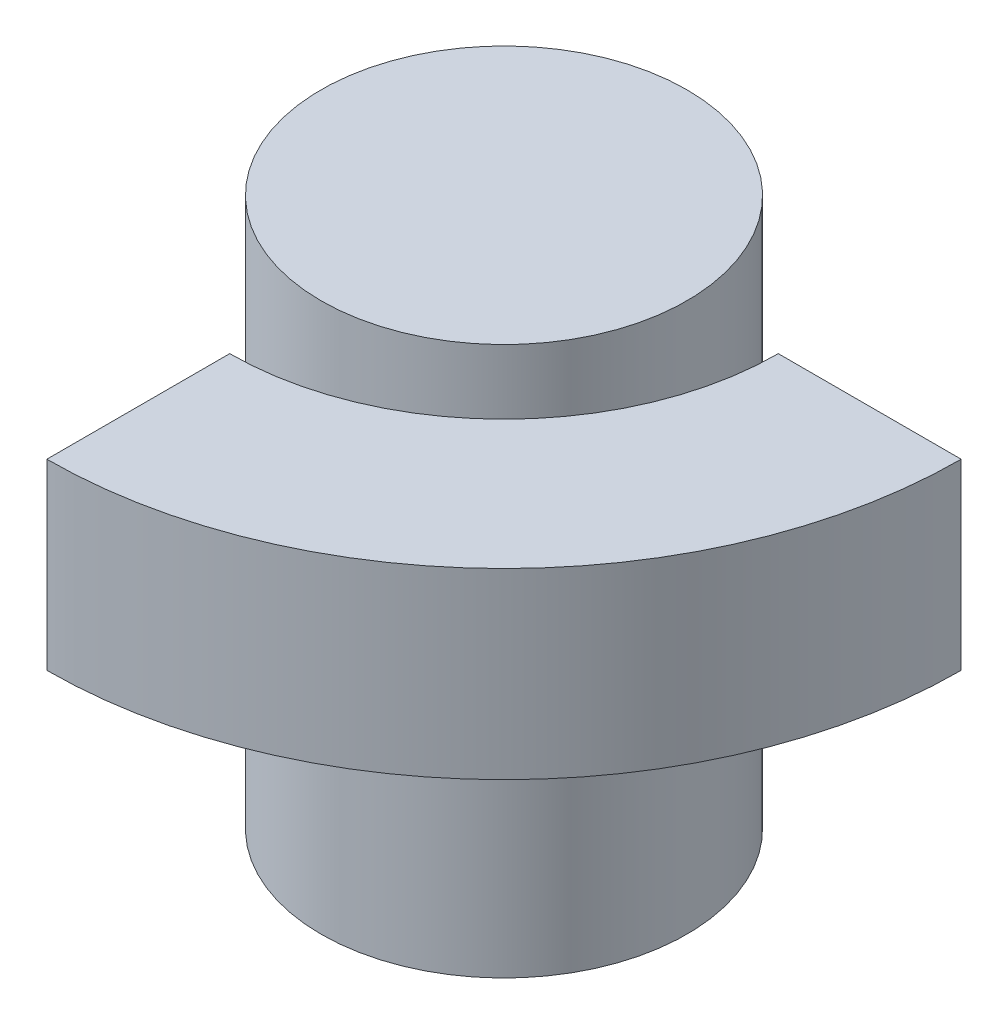
SolidWorks part; units mm, degrees
ref_plane "Front Plane" through (0, 0, 0) normal (0, 0, 1) x (1, 0, 0)
ref_plane "Top Plane" through (0, 0, 0) normal (0, 1, 0) x (1, 0, 0)
ref_plane "Right Plane" through (0, 0, 0) normal (1, 0, 0) x (0, 0, -1)
sketch "Sketch1" plane through (0, 0, 0) normal (0, 1, 0) x (1, 0, 0)
  circle A0 centre (20, 0) radius 10
extrude "Boss-Extrude1" add sketch "Sketch1" along normal blind 15 and the other way blind 15
sketch "Sketch2" plane through (0, 0, 0) normal (0, 0, 1) x (1, 0, 0)
  line L1 (35, 5) -> (45, 5)
  line L2 (35, 5) -> (35, 15)
  line L3 (35, 15) -> (45, 15)
  line L4 (45, 5) -> (45, 15)
revolve "Revolve1" add sketch "Sketch2" angle 90 about axis through (20, -15, 0) along (0, 1, 0) reverse direction yes
